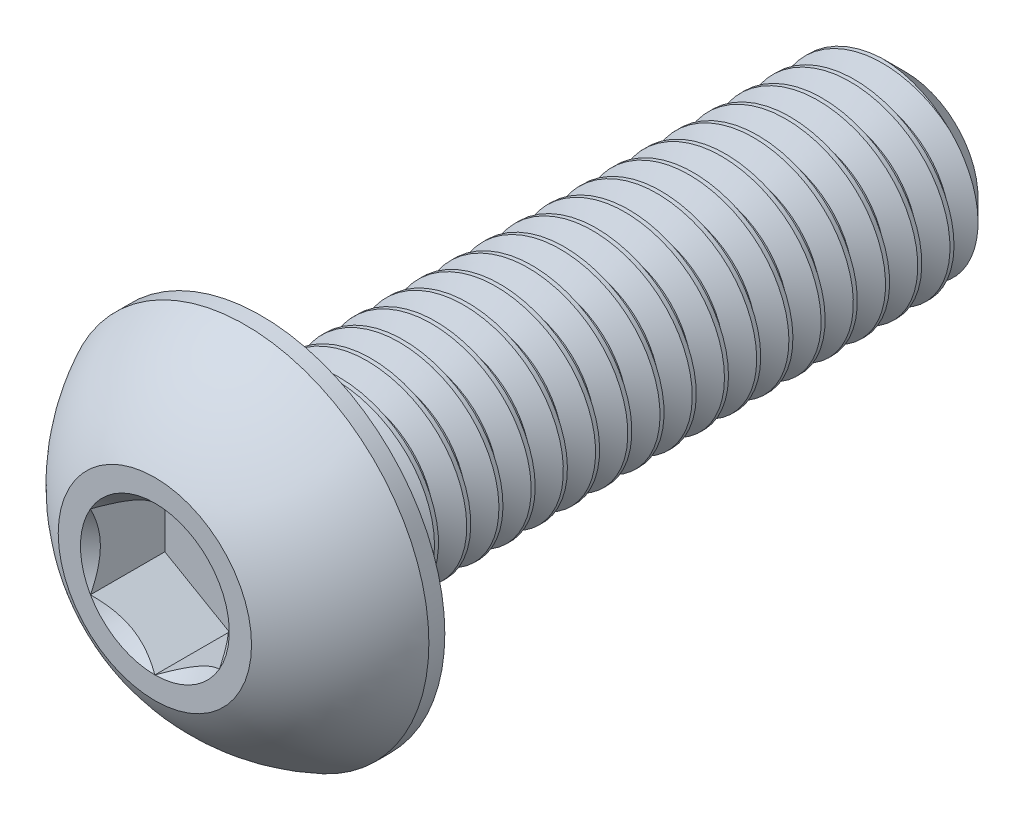
SolidWorks part; units mm, degrees
note: '?' marks a value the reader was unsure of.
ref_plane "Front" through (0, 0, 0) normal (0, 0, 1) x (1, 0, 0)
ref_plane "Top" through (0, 0, 0) normal (0, 1, 0) x (1, 0, 0)
ref_plane "Right" through (0, 0, 0) normal (1, 0, 0) x (0, 0, -1)
sketch "Sketch1" plane through (0, 0, 0) normal (1, 0, 0) x (0, 0, -1)
  line L2 (1.65, 1.5) -> (11.65, 1.5)
  line L3 (11.65, 1.5) -> (11.65, 0)
  line L4 (11.65, 0) -> (1.65, 0)
  line L6 (1.4025, 2.85) -> (1.65, 2.85) construction
  line L7 (11.65, 1.5) -> (11.65, -1.5) construction
  line L8 (0, 0) -> (1.65, 0) construction
  line L9 (1.65, 2.85) -> (1.65, -2.85) construction
  line L11 (1.65, 1.5) -> (1.65, 0)
  line L13 (0, 1) -> (0, -1) construction
  line L14 (0, 1) -> (0, 1.5) construction
  arc A3 (0, 1.5) -> (1.4025, 2.85) centre (2.7948, 0) cw construction
  dimension "D1" = 0.2475
  dimension "Head Ht" = 1.65
  dimension "Head Dia" = 5.7
  dimension "Dia" = 3
  dimension "Lg" = 10
  dimension "Hex" = 2
revolve "Revolve1" add sketch "Sketch1" angle 360 mid plane about L4
sketch "Sketch3" plane through (0, 0, -11.65) normal (0, 0, -1) x (-1, 0, 0)
  circle A0 centre (0, 0) radius 1.5
curve "Helix/Spiral1" pitch 0.5 height 10.5 turns 21
chamfer "Chamfer1" distance 0.375 angle 45 1 edges at (0, 1.5, -11.65)
sketch "Sketch7" plane through (0, 0, 0) normal (1, 0, 0) x (0, 0, -1)
  line L6 (1.4025, 2.85) -> (1.65, 2.85) construction
  line L8 (0, 0) -> (1.65, 0) construction
  line L11 (1.65, 2.85) -> (1.65, -2.85) construction
  line L12 (1.4025, 2.85) -> (1.65, 2.85)
  line L13 (0, 0) -> (1.65, 0)
  line L14 (0, 1) -> (0, -1) construction
  line L15 (1.65, 2.85) -> (1.65, 0)
  line L16 (0, 1.5) -> (0, 0)
  arc A2 (1.4025, 2.85) -> (0, 1.5) centre (2.7948, 0) ccw construction
  arc A3 (1.4025, 2.85) -> (0, 1.5) centre (2.7948, 0) ccw
revolve "Revolve2" add sketch "Sketch7" angle 360 mid plane about L13
sketch "Sketch5" plane through (0, 0, 0) normal (0, 0, 1) x (1, 0, 0)
  line L1 (1, -0.5774) -> (1, 0.5774)
  line L2 (1, 0.5774) -> (0, 1.1547)
  line L3 (0, 1.1547) -> (-1, 0.5774)
  line L4 (-1, 0.5774) -> (-1, -0.5774)
  line L5 (-1, -0.5774) -> (0, -1.1547)
  line L6 (0, -1.1547) -> (1, -0.5774)
  circle A0 centre (0, 0) radius 1 construction
extrude "Cut-Extrude2" cut sketch "Sketch5" against normal blind 1.155
sketch "Sketch6" plane through (0, 0, 0) normal (0, 0, 1) x (1, 0, 0)
  circle A0 centre (0, 0) radius 1.1547
extrude "Cut-Extrude3" cut sketch "Sketch6" against normal blind 1.155 draft 45
sketch "Sketch2" plane through (0, 0, 0) normal (1, 0, 0) x (0, 0, -1)
  line L0 (11.275, 1.5) -> (11.7125, 1.5)
  line L1 (11.7125, 1.5) -> (11.525, 1.1752)
  line L2 (11.525, 1.1752) -> (11.4625, 1.1752)
  line L3 (11.4625, 1.1752) -> (11.275, 1.5)
  line L4 (11.3688, 1.3376) -> (11.6188, 1.3376) construction
  dimension "D1" = 60
  dimension "D2" = 0.0625
  dimension "D3" = 0.25
sweep "Cut-Sweep1" cut profiles "Sketch2" path "Helix/Spiral1"
sketch "Sketch10" plane through (0, 0, 0) normal (1, 0, 0) x (0, 0, -1)
  line L0 (11.65, 1.5) -> (11.65, -1.5) construction
  point P0 (10.9, -1.5)
  dimension "D1" = 0.75
ref_axis "Center Axis 1" through (0, 0, -8.1113) along (0, 0, 1)?
ref_plane "Contact Plane 1" through (0, 0, -1.65) normal (0, 0, -1) x (-1, 0, 0)
ref_plane "Contact Plane 2" through (0, 0, 0) normal (0, 0, 1) x (1, 0, 0)
equation "\"D3@Helix/Spiral1\" = \"Lg@Sketch1\" + \"D4@Helix/Spiral1\""
equation "\"D2@Sketch2\" = \"D4@Helix/Spiral1\" * .125"
equation "\"D3@Sketch2\" = \"D4@Helix/Spiral1\" * .5"
equation "\"D1@Chamfer1\" = \"D4@Helix/Spiral1\" * .75"
equation "\"D1@Cut-Extrude2\" = \"Head Ht@Sketch1\" * .7"
equation "\"D1@Sketch1\" = \"Head Ht@Sketch1\" * .15"
equation "\"D1@Sketch10\" = \"D4@Helix/Spiral1\" * 1.5"
equation "\"D1@Cut-Extrude3\" = \"D1@Cut-Extrude2\""
